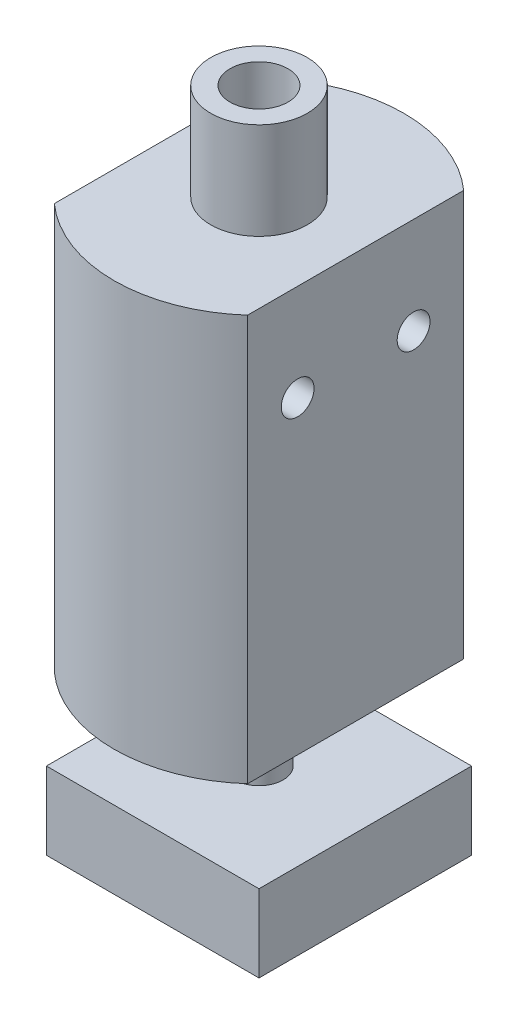
SolidWorks part; units mm, degrees
ref_plane "前视基准面" through (0, 0, 0) normal (0, 0, 1) x (1, 0, 0)
ref_plane "上视基准面" through (0, 0, 0) normal (0, 1, 0) x (1, 0, 0)
ref_plane "右视基准面" through (0, 0, 0) normal (1, 0, 0) x (0, 0, -1)
sketch "草图1" plane through (0, 0, 0) normal (0, 0, 1) x (1, 0, 0)
  line L0 (2.5, 0) -> (15, 0)
  line L1 (15, 0) -> (15, 42)
  line L2 (15, 42) -> (5, 42)
  line L3 (0, 0) -> (0, 42)
  line L4 (5, 42) -> (5, 52)
  line L5 (5, 52) -> (3, 52)
  line L6 (3, 52) -> (3, 42)
  line L7 (3, 42) -> (0, 42)
  line L8 (2.5, 0) -> (2.5, -19.0163)
  line L9 (0.2, -23) -> (0, -23)
  line L10 (0, -23) -> (0, 0)
  line L11 (0.2, -23) -> (2.5, -19.0163)
  dimension "D1" = 3
  dimension "D2" = 15
  dimension "D3" = 10
  dimension "D4" = 42
  dimension "D5" = 5
  dimension "D6" = 23
  dimension "D7" = 2.5
  dimension "D8" = 60
  dimension "D9" = 0.2
revolve "旋转1" add sketch "草图1" angle 360 about L3
sketch "草图2" plane through (0, 0, 0) normal (0, 0, 1) x (1, 0, 0)
  line L1 (-10, -23) -> (10, -23)
  line L2 (-10, -23) -> (-10, 52)
  line L3 (-10, 52) -> (10, 52)
  line L4 (10, -23) -> (10, 52)
  line L5 (-10, -23) -> (10, 52) construction
  line L6 (-10, 52) -> (10, -23) construction
  line L10 (3, 52) -> (-3, 52) construction
  line L11 (-2.5, -23) -> (2.5, -23) construction
  point P0 (0, 14.5)
  dimension "D1" = 20
extrude "切除-拉伸2" cut sketch "草图2" against normal through all and the other way through all flip side to cut contours L3 L4 L1 L2
sketch "草图4" plane through (0, 0, 0) normal (0, 0, 1) x (1, 0, 0)
  line L1 (-11, -17) -> (11, -17)
  line L2 (-11, -17) -> (-11, -9)
  line L3 (-11, -9) -> (11, -9)
  line L4 (11, -17) -> (11, -9)
  line L5 (-11, -17) -> (11, -9) construction
  line L6 (-11, -9) -> (11, -17) construction
  point P0 (0, -13)
  dimension "D1" = 22
  dimension "D2" = 8
  dimension "D3" = 13
extrude "凸台-拉伸1" add sketch "草图4" along normal blind 11 and the other way blind 11
sketch "草图5" plane through (10, 0, 0) normal (1, 0, 0) x (0, 0, -1)
  line L0 (0, -1000) -> (0, 49000) construction
  line L1 (-11.1803, 42) -> (11.1803, 42) construction
  circle A0 centre (-6, 32) radius 1.7
  circle A1 centre (6, 32) radius 1.7
  dimension "D1" = 3.4
  dimension "D2" = 12
  dimension "D3" = 10
extrude "切除-拉伸3" cut sketch "草图5" against normal through all
